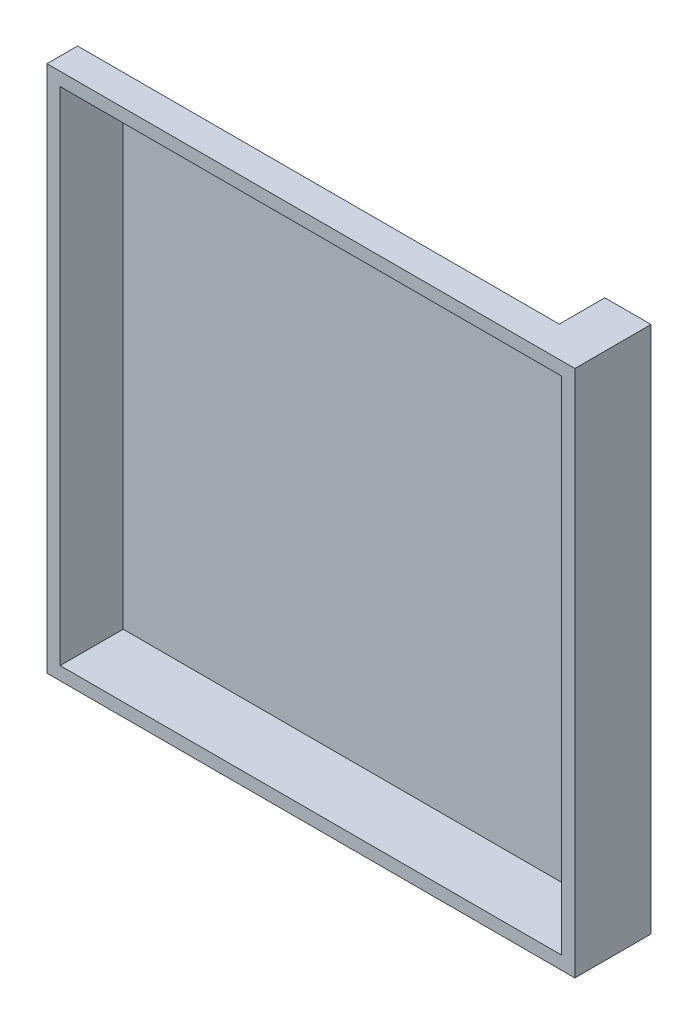
SolidWorks part; units mm, degrees
other "Marquage1"
sketch "Esquisse19" plane through (-200, 200, 1200) normal (-0.9945, 0.0821, 0.065) x (0.0675, 0.9772, -0.2013)
ref_plane "Plan de face" through (0, 0, 0) normal (0, 0, 1) x (1, 0, 0)
ref_plane "Plan de dessus" through (0, 0, 0) normal (0, 1, 0) x (1, 0, 0)
ref_plane "Plan de droite" through (0, 0, 0) normal (1, 0, 0) x (0, 0, -1)
sketch "Esquisse1" plane through (0, 0, 0) normal (0, 0, 1) x (1, 0, 0)
  line L1 (-200, 200) -> (200, 200)
  line L2 (-200, 200) -> (-200, -200)
  line L3 (-200, -200) -> (200, -200)
  line L4 (200, 200) -> (200, -200)
  line L5 (-200, 200) -> (200, -200) construction
  line L6 (-200, -200) -> (200, 200) construction
  point P0 (0, 0)
  dimension "D1" = 400
  dimension "D2" = 400
extrude "Boss.-Extru.1" add sketch "Esquisse1" along normal blind 1200
sketch "Esquisse4" plane through (0, 200, 0) normal (0, 1, 0) x (1, 0, 0)
  line L0 (200, -1200) -> (200, 0) construction
  line L1 (-200, -1142.265) -> (200, -1142.265)
  line L2 (-200, -1142.265) -> (-200, -1011.665)
  line L3 (-200, -1011.665) -> (200, -1011.665)
  line L4 (200, -1142.265) -> (200, -1011.665)
  line L6 (-200, -1200) -> (200, -1200)
  line L8 (200, -1200) -> (200, 0)
  line L9 (200, 0) -> (-200, 0)
  line L10 (-200, 0) -> (-200, -1200)
  line L11 (-200, -1200) -> (200, -1200)
  line L15 (200, 0) -> (-200, 0)
  line L16 (-200, 0) -> (-200, -1200)
  point P12 (200, -1011.665)
  point P15 (-200, -1011.665)
  dimension "D2" = 400
  dimension "D5" = 130.6
  dimension "D1" = 0
extrude "Enlèv. mat.-Extru.1" cut sketch "Esquisse4" against normal blind 300 contours L2 L4 L3 region at (0, 200, 1076.965)
sketch "Esquisse5" plane through (0, -200, 0) normal (0, -1, 0) x (1, 0, 0)
  line L3 (-200, 0) -> (-200, 1200) construction
  line L4 (200, 1142.265) -> (-200, 1142.265)
  line L5 (200, 1011.665) -> (200, 1142.265)
  line L6 (-200, 1011.665) -> (200, 1011.665)
  line L7 (-200, 1142.265) -> (-200, 1011.665)
  line L8 (200, 1142.265) -> (-200, 1142.265)
  line L12 (200, 0) -> (-200, 0) construction
  line L13 (198, 1142.265) -> (200, 1144.5744)
  line L14 (-198, 1142.265) -> (198, 1142.265)
  line L15 (-200, 1200) -> (-198, 1142.265)
  line L16 (-200, 0) -> (-200, 1200)
  line L17 (200, 0) -> (-200, 0)
  line L18 (0, 1341.3483) -> (0, 256.7577) construction
  line L19 (200, 1200) -> (200, 0) construction
  line L20 (-145, 902.265) -> (145, 902.265)
  line L21 (-160, 887.265) -> (-160, 797.265)
  line L22 (-145, 782.265) -> (145, 782.265)
  line L23 (160, 887.265) -> (160, 797.265)
  line L24 (-160, 902.265) -> (160, 782.265) construction
  line L25 (-160, 782.265) -> (160, 902.265) construction
  line L32 (-150, 417.265) -> (-144, 420.265) construction
  arc A0 (145, 782.265) -> (160, 797.265) centre (145, 797.265) ccw
  arc A1 (145, 902.265) -> (160, 887.265) centre (145, 887.265) cw
  arc A6 (-145, 902.265) -> (-160, 887.265) centre (-145, 887.265) ccw
  arc A7 (-160, 797.265) -> (-145, 782.265) centre (-145, 797.265) ccw
  point P15 (0, 842.265)
  point P35 (0, 492.265)
  dimension "D5" = 15
  dimension "D2" = 320
  dimension "D3" = 120
  dimension "D4" = 200
  dimension "D6" = 300
  dimension "D1" = 0
extrude "Enlèv. mat.-Extru.2" cut sketch "Esquisse5" against normal blind 100 contours L21 A7 L22 A0 L23 A1 L20 A6
sketch "Esquisse13" plane through (0, 0, 0) normal (0, 0, -1) x (-1, 0, 0)
  line L4 (-200, 200) -> (-200, -200)
  line L5 (-200, -200) -> (200, -200)
  line L6 (200, -200) -> (200, 200)
  line L7 (200, 200) -> (-200, 200)
  line L8 (-200, 200) -> (-200, -200)
  line L9 (-200, -200) -> (200, -200)
  line L10 (200, -200) -> (200, 200)
  line L11 (200, 200) -> (-200, 200)
  dimension "D1" = 0
extrude "Enlèv. mat.-Extru.10" cut sketch "Esquisse13" against normal blind 400
sketch "Esquisse15" plane through (0, 0, 1142.265) normal (0, 0, -1) x (-1, 0, 0)
  line L0 (-0.0112, -20) -> (-0.0112, -19.762) construction
  line L1 (0, 328.0531) -> (0, -138.9758) construction
  line L2 (-0.0112, -20) -> (-0.0112, -19.762) construction
  line L3 (-150, 200) -> (-150, -100)
  line L4 (150, 200) -> (150, -100)
  line L13 (-150, 200) -> (-200, 200)
  line L14 (200, 200) -> (-200, 200)
  line L15 (-200, 200) -> (-200, -100)
  line L16 (-200, -100) -> (200, -100)
  line L17 (200, -100) -> (200, 200)
  line L18 (200, 200) -> (48.3322, 200)
  line L19 (-200, 200) -> (-200, -100)
  line L20 (-200, -100) -> (200, -100)
  line L21 (200, -100) -> (200, 200)
  arc A1 (-147.0297, 28.297) -> (147.0297, 28.297) centre (0, 58) ccw
  arc A6 (-150, 18.9488) -> (150, 18.9488) centre (0, 58) ccw
  arc A8 (-155, 58) -> (155, 58) centre (0, 58) ccw construction
  arc A9 (150, 28) -> (147.0297, 28.297) centre (148.5, 28) ccw
  arc A10 (-150, 28) -> (-147.0297, 28.297) centre (-148.5, 28) cw
  arc A11 (-150, 58) -> (150, 58) centre (0, 58) ccw construction
  dimension "D4" = 5
  dimension "D3" = 158
  dimension "D5" = 3
  dimension "D2" = 50
  dimension "D1" = 0
ref_plane "Plan1" through (165, 0, 0) normal (1, 0, 0) x (0, 0, -1)
sketch "Esquisse16" plane through (165, 0, 0) normal (1, 0, 0) x (0, 0, -1)
  line L0 (-1200, 200) -> (-1142.265, 200) construction
  line L1 (-1142.265, -100) -> (-1142.265, 200) construction
  arc A0 (-1171.1325, 200) -> (-1142.265, 178.228) centre (-1154.1519, 192.4908) ccw
sketch "Esquisse18" plane through (200, 0, 0) normal (1, 0, 0) x (0, 0, -1)
  line L0 (-1132.265, 319.4005) -> (-1132.265, -35.6293) construction
  line L1 (-1224.6221, 190) -> (-1055.3575, 190) construction
  line L2 (-1200, 200) -> (-1142.265, 200)
  line L3 (-1200, 200) -> (-1142.265, 200) construction
  line L8 (-400, -200) -> (-400, 200)
  line L9 (-400, 200) -> (-1011.665, 200)
  line L10 (-1011.665, 200) -> (-1011.665, -100)
  line L11 (-1011.665, -100) -> (-1142.265, -100)
  line L12 (-1142.265, -100) -> (-1142.265, 200)
  line L13 (-1142.265, 200) -> (-1200, 200)
  line L14 (-1200, 200) -> (-1200, -200)
  line L15 (-1200, -200) -> (-400, -200)
  line L16 (-400, -200) -> (-400, 200)
  line L17 (-400, 200) -> (-1011.665, 200)
  line L18 (-1011.665, 200) -> (-1011.665, -100)
  line L19 (-1011.665, -100) -> (-1142.265, -100)
  line L20 (-1142.265, 153.8579) -> (-1142.265, 200)
  line L23 (-1200, -200) -> (-400, -200)
  arc A1 (-1176.7931, 200) -> (-1142.265, 162.6252) centre (-1132.265, 206.5) ccw
  line M14 (-1142.265, -100) -> (-1142.265, 200)
  line M15 (-1142.265, 200) -> (-1200, 200)
  dimension "D2" = 10
  dimension "D3" = 90
  dimension "D4" = 16.5
  dimension "D1" = 0
extrude "Enlèv. mat.-Extru.11" cut sketch "Esquisse18" against normal blind 400 from offset 35 contours M15 M14 region at (200, 185.0522, 1156.1758) offset against normal yes
fillet "Congé3" radius 10 1 edges at (-17.5, 162.6252, 1142.265)
sketch "Esquisse20" plane through (0, -200, 0) normal (0, -1, 0) x (1, 0, 0)
  line L0 (0, 0) -> (0, 736.7231) construction
  line L2 (-155, 703.3933) -> (155, 703.3933)
  line L3 (-175, 683.3933) -> (-175, 400)
  line L4 (-200, 400) -> (200, 400)
  line L5 (200, 400) -> (200, 1200)
  line L6 (200, 1200) -> (-200, 1200)
  line L7 (-200, 1200) -> (-200, 400)
  line L8 (-200, 400) -> (200, 400)
  line L9 (200, 400) -> (200, 1200)
  line L10 (200, 1200) -> (-200, 1200)
  line L11 (-200, 1200) -> (-200, 400)
  line L12 (-175, 400) -> (175, 400)
  line L13 (175, 683.3933) -> (175, 400)
  line L14 (-175, 703.3933) -> (175, 400) construction
  line L15 (-175, 400) -> (175, 703.3933) construction
  arc A0 (155, 703.3933) -> (175, 683.3933) centre (155, 683.3933) cw
  arc A1 (-155, 703.3933) -> (-175, 683.3933) centre (-155, 683.3933) ccw
  point P6 (0, 551.6967)
  line M17 (-200, 400) -> (200, 400)
  dimension "D3" = 20
  dimension "D2" = 25
  dimension "D1" = 0
extrude "Enlèv. mat.-Extru.12" cut sketch "Esquisse20" against normal blind 100 contours L2 A1 L3 L13 A0 M17 region at (0, -200, 551.4582)
fillet "Congé5" radius 5 3 edges at (-175, -150, 400) (0, -100, 400) (175, -150, 400)
shell "Coque1" thickness 10 removed face at (0, 0, 1200)
sketch "Esquisse21" plane through (0, 0, 1011.665) normal (0, 0, 1) x (1, 0, 0)
  line L4 (200, 200) -> (-200, 200)
  line L5 (-200, 200) -> (-200, -100)
  line L6 (-200, -100) -> (200, -100)
  line L7 (200, -100) -> (200, 200)
  line L8 (200, 200) -> (-200, 200)
  line L9 (-200, 200) -> (-200, -100)
  line L10 (-200, -100) -> (200, -100)
  line L11 (200, -100) -> (200, 200)
  line L14 (180, 180) -> (-180, 180)
  line L15 (-180, 180) -> (-180, -80)
  line L16 (-180, -80) -> (180, -80)
  line L17 (180, -80) -> (180, 180)
  dimension "D1" = 0
  dimension "D2" = 20
extrude "Enlèv. mat.-Extru.13" cut sketch "Esquisse21" against normal blind 300 contours L14 L15 L16 L17
sketch "Esquisse22" plane through (0, 0, 1011.665) normal (0, 0, 1) x (1, 0, 0)
  line L0 (180, 180) -> (-180, 180) construction
  line L1 (180, 180) -> (-180, 180)
  line L2 (-180, 180) -> (-200, 180)
  line L3 (-200, 180) -> (200, 180)
  line L4 (200, 200) -> (-200, 200)
  line L5 (-200, 200) -> (-200, -100)
  line L6 (-200, -100) -> (200, -100)
  line L7 (200, -100) -> (200, 200)
  line L8 (200, 200) -> (-200, 200)
  line L9 (-200, 200) -> (-200, 180)
  line L10 (-200, -100) -> (200, -100)
  line L11 (200, 180) -> (200, 200)
  line M8 (-180, 180) -> (180, 180)
  line M9 (200, 200) -> (-200, 200)
  line M10 (-200, 200) -> (-200, -100)
  line M12 (200, -100) -> (200, 200)
  dimension "D1" = 0
extrude "Enlèv. mat.-Extru.14" cut sketch "Esquisse22" against normal through all contours L3 L2 M8 M12 M9 M10 region at (0, 190, 1011.665)
sketch "Esquisse23" plane through (0, 180, 0) normal (0, 1, 0) x (1, 0, 0)
  line L0 (-190, -410) -> (-200, -410)
  line L1 (190, -410) -> (200, -410)
  line L12 (-190, -1001.665) -> (-190, -410)
  line L13 (-190, -410) -> (190, -410)
  line L14 (190, -410) -> (190, -1001.665)
  line L15 (190, -1001.665) -> (180, -1001.665)
  line L16 (180, -1001.665) -> (180, -1011.665)
  line L17 (180, -1011.665) -> (200, -1011.665)
  line L18 (200, -1011.665) -> (200, -400)
  line L19 (200, -400) -> (-200, -400)
  line L20 (-200, -400) -> (-200, -1011.665)
  line L21 (-200, -1011.665) -> (-180, -1011.665)
  line L22 (-180, -1011.665) -> (-180, -1001.665)
  line L23 (-180, -1001.665) -> (-190, -1001.665)
  line L24 (-190, -1001.665) -> (-190, -410)
  line L25 (-190, -410) -> (190, -410)
  line L26 (190, -410) -> (190, -1001.665)
  line L27 (190, -1001.665) -> (180, -1001.665)
  line L28 (180, -1001.665) -> (180, -1011.665)
  line L29 (180, -1011.665) -> (200, -1011.665)
  line L30 (200, -1011.665) -> (200, -400)
  line L31 (200, -400) -> (-200, -400)
  line L32 (-200, -400) -> (-200, -1011.665)
  line L33 (-200, -1011.665) -> (-180, -1011.665)
  line L34 (-180, -1011.665) -> (-180, -1001.665)
  line L35 (-180, -1001.665) -> (-190, -1001.665)
  line M14 (-190, -410) -> (190, -410)
  line M19 (200, -1011.665) -> (200, -400)
  line M20 (200, -400) -> (-200, -400)
  line M21 (-200, -400) -> (-200, -1011.665)
  dimension "D1" = 0
extrude "Enlèv. mat.-Extru.15" cut sketch "Esquisse23" against normal up to surface (280 mm away) contours L1 L0 M14 M19 M20 M21 region at (0, 180, 405) up to face at (0, -100, 598.6429)
sketch "Esquisse24" plane through (0, -200, 0) normal (0, -1, 0) x (1, 0, 0)
  line L0 (-200, 1142.265) -> (200, 1142.265) construction
  line L1 (-200, 1142.265) -> (200, 1142.265)
  line L2 (-200, 1200) -> (-200, 400) construction
  line L3 (-200, 1142.265) -> (-200, 400)
  line L4 (200, 1200) -> (200, 400) construction
  line L5 (200, 1142.265) -> (200, 400)
  line L6 (-200, 400) -> (200, 400)
extrude "Enlèv. mat.-Extru.16" cut sketch "Esquisse24" against normal through all
sketch "Esquisse25" plane through (0, -110, 0) normal (0, -1, 0) x (1, 0, 0)
  line L4 (-190, 1152.265) -> (-190, 1142.265)
  line L5 (-190, 1142.265) -> (190, 1142.265)
  line L6 (190, 1142.265) -> (190, 1152.265)
  line L7 (190, 1152.265) -> (-190, 1152.265)
  line L8 (-190, 1152.265) -> (-190, 1142.265)
  line L9 (-190, 1142.265) -> (190, 1142.265)
  line L10 (190, 1142.265) -> (190, 1152.265)
  line L11 (190, 1152.265) -> (-190, 1152.265)
  dimension "D1" = 0
extrude "Boss.-Extru.2" add sketch "Esquisse25" along normal through all
